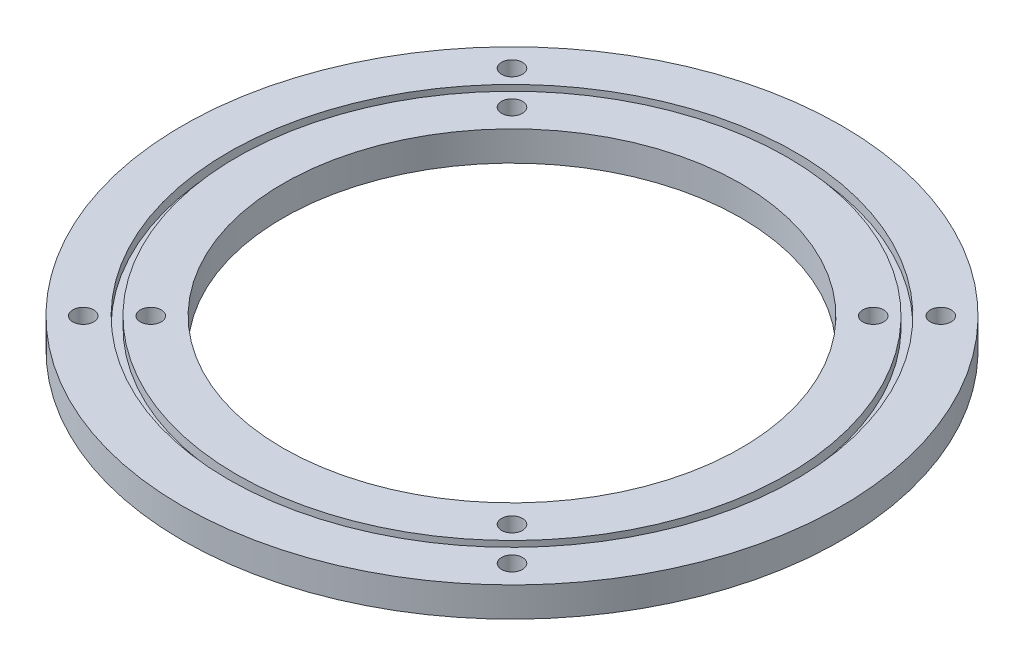
SolidWorks part; units mm, degrees
ref_plane "Front Plane" through (0, 0, 0) normal (0, 0, 1) x (1, 0, 0)
ref_plane "Top Plane" through (0, 0, 0) normal (0, 1, 0) x (1, 0, 0)
ref_plane "Right Plane" through (0, 0, 0) normal (1, 0, 0) x (0, 0, -1)
sketch "Sketch1" plane through (0, 0, 0) normal (0, 1, 0) x (1, 0, 0)
  line L0 (0, 0) -> (54.8008, 54.8008) construction
  line L1 (-69.5, 0) -> (-84.75, 0) construction
  line L2 (-84.75, 0) -> (-100, 0) construction
  line L3 (59.9273, 59.9273) -> (22.3944, 97.4602) construction
  circle A0 centre (0, 0) radius 100
  circle A1 centre (0, 0) radius 69.5
  circle A2 centre (54.8008, 54.8008) radius 3.175
  circle A3 centre (0, 0) radius 84.75 construction
  circle A4 centre (0, 0) radius 86.02
  circle A5 centre (0, 0) radius 83.48
  circle A6 centre (65.0538, 65.0538) radius 3.175
  circle A7 centre (65.0538, -65.0538) radius 3.175
  circle A8 centre (54.8008, -54.8008) radius 3.175
  circle A9 centre (-65.0538, -65.0538) radius 3.175
  circle A10 centre (-54.8008, -54.8008) radius 3.175
  circle A11 centre (-65.0538, 65.0538) radius 3.175
  circle A12 centre (-54.8008, 54.8008) radius 3.175
  point P33 (0, 0)
  dimension "D1" = 200
  dimension "D2" = 139
  dimension "D4" = 6.35
  dimension "D7" = 4
  dimension "D3" = 77.5
  dimension "D8" = 45
  dimension "D5" = 1.27
  dimension "D6" = 1.27
extrude "Boss-Extrude1" add sketch "Sketch1" along normal mid plane 9 contours A0 A9 A6 A4 A7 A11 | A5 A12 A10 A8 A2 A1 region at (-97.1716, 0, 0) region at (-81.1188, 0, 0)
extrude "Boss-Extrude2" add sketch "Sketch1<3>" along normal mid plane 3.175 contours A4 A5 region at (-83.587, 0, 0)
sketch "Sketch1<3>" plane through (0, 0, 0) normal (0, 1, 0) x (1, 0, 0) same geometry as "Sketch1"
